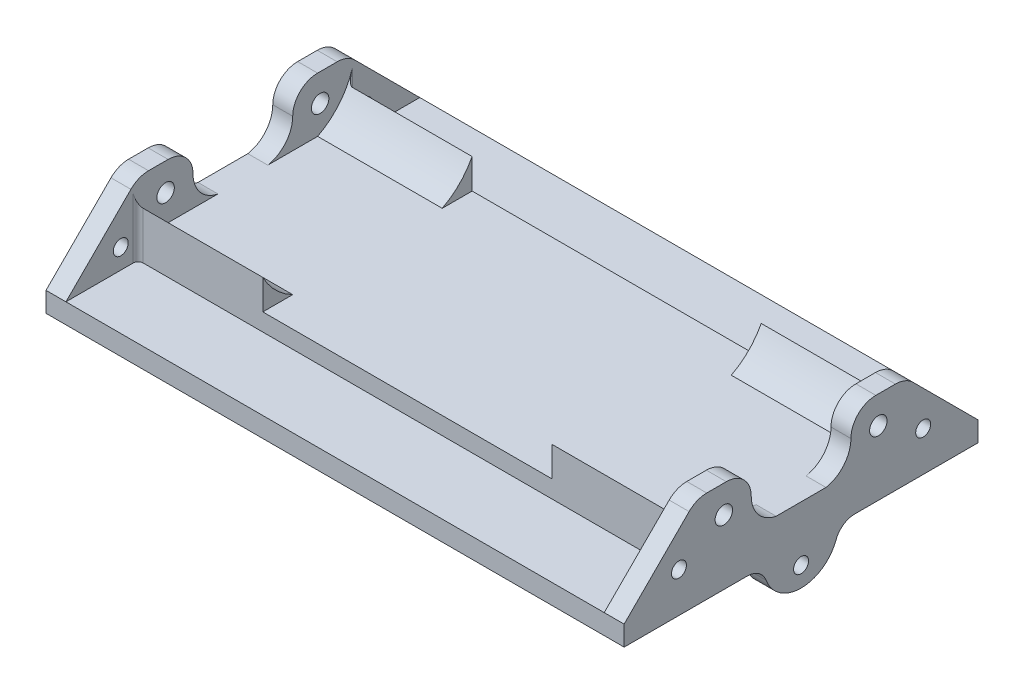
SolidWorks part; units mm, degrees
ref_plane "Front Plane" through (0, 0, 0) normal (0, 0, 1) x (1, 0, 0)
ref_plane "Top Plane" through (0, 0, 0) normal (0, 1, 0) x (1, 0, 0)
ref_plane "Right Plane" through (0, 0, 0) normal (1, 0, 0) x (0, 0, -1)
sketch "Sketch1" plane through (0, 0, 0) normal (0, 1, 0) x (1, 0, 0)
  line L1 (-58, -21) -> (58, -21)
  line L2 (-58, -21) -> (-58, 21)
  line L3 (-58, 21) -> (58, 21)
  line L4 (58, -21) -> (58, 21)
  line L5 (-58, -21) -> (58, 21) construction
  line L6 (-58, 21) -> (58, -21) construction
  point P0 (0, 0)
  dimension "D1" = 42
  dimension "D2" = 116
extrude "Boss-Extrude1" add sketch "Sketch1" along normal blind 3.5 from offset 3.5
sketch "Sketch2" plane through (0, 0, 0) normal (1, 0, 0) x (0, 0, -1)
  line L0 (-21, 7) -> (21, 7) construction
  line L1 (-21, 7) -> (21, 7)
  line L2 (0, 0) -> (0, 30.7392) construction
  line L3 (-21, 7) -> (-21, 54.5)
  line L4 (21, 7) -> (21, 54.5)
  line L5 (21, 48.95) -> (-21, 48.95)
  line L6 (21, 30.75) -> (-29.0104, 30.75) construction
  line L7 (21, 7) -> (10, 7)
  line L8 (21, 7) -> (21, 18)
  line L9 (21, 18) -> (15, 18)
  line L11 (10, 7) -> (0, 7)
  line L12 (-21, 18) -> (-15, 18)
  arc A0 (15, 18) -> (10, 13) centre (15, 13) ccw
  arc A1 (10, 13) -> (5, 7) centre (3.9, 13) cw
  arc A2 (-10, 13) -> (-5, 7) centre (-3.9, 13) ccw
  arc A3 (-15, 18) -> (-10, 13) centre (-15, 13) cw
  point P16 (10, 18)
  line B0 (-25, 54.5) -> (-25, 39.5)
  line B1 (25, 54.5) -> (-25, 54.5)
  line B2 (25, 54.5) -> (25, 39.5)
  line B3 (25, 7) -> (25, 39.5)
  line B4 (25, 7) -> (-25, 7)
  line B5 (-25, 7) -> (-25, 39.5)
  circle B6 centre (-15.5, 43.475) radius 1.75
  circle B7 centre (15.5, 43.475) radius 1.75
  circle B8 centre (15.5, 12.475) radius 1.75
  circle B9 centre (0, 27.975) radius 11.075
  circle B10 centre (-15.5, 12.475) radius 1.75
  dimension "D3" = 5
  dimension "D1" = 41.95
  dimension "D2" = 11
sketch_block_instance "Block1-2"
sketch_block "Block1"
extrude "Boss-Extrude2" add sketch "Sketch2" along normal up to surface and the other way up to surface contours A0 A1 L11 L1 L4 L9 B8 | A3 L12 L3 L1 A2 B10 region at (0, 12.5, 20.8058) region at (0, 8.9706, -8.7353) up to face at (58, 5.25, 0) other way up to face at (-58, 5.25, 0)
extrude "Cut-Extrude1" cut sketch "Sketch2<3>" against normal mid plane 108 contours A0 A1 L11 L1 L4 L9 B8 | A3 L12 L3 L1 A2 B10 region at (0, 12.5, 20.8058) region at (0, 8.9706, -8.7353)
sketch "Sketch2<3>" plane through (0, 0, 0) normal (1, 0, 0) x (0, 0, -1) same geometry as "Sketch2"
sketch "Sketch3" plane through (-54, 0, 0) normal (1, 0, 0) x (0, 0, -1)
  line L0 (-21, 7) -> (-15, 7)
  line L1 (-21, 7) -> (-21, 13)
  line L2 (-21, 18) -> (-21, 3.5) construction
  line L3 (0, 0) -> (0, 17.1319) construction
  line L4 (21, 7) -> (21, 13)
  line L5 (21, 7) -> (15, 7)
  arc A0 (-15, 7) -> (-21, 13) centre (-8.566, 19.434) cw
  arc A1 (15, 7) -> (21, 13) centre (8.566, 19.434) ccw
  dimension "D3" = 14
  dimension "D1" = 6
  dimension "D2" = 6
extrude "Boss-Extrude3" add sketch "Sketch3" along normal blind 25
mirror "Mirror4" about plane through (0, 0, 0) normal (1, 0, 0) of "Boss-Extrude3"
sketch "Sketch4" plane through (-58, 0, 0) normal (-1, 0, 0) x (0, 0, 1)
  line L0 (21, 18) -> (35.5, 3.5)
  line L1 (35.5, 3.5) -> (21, 3.5)
  line L2 (0, 3.5) -> (0, 12.4204) construction
  line L3 (-21, 3.5) -> (21, 3.5) construction
  line L4 (21, 18) -> (21, 3.5)
  line L5 (-21, 18) -> (-21, 3.5)
  line L6 (-35.5, 3.5) -> (-21, 3.5)
  line L7 (-21, 18) -> (-35.5, 3.5)
  circle A0 centre (24.5, 7.5) radius 1.5
  circle A1 centre (-24.5, 7.5) radius 1.5
  dimension "D2" = 3
  dimension "D1" = 14.5
  dimension "D3" = 4
  dimension "D4" = 3.5
extrude "Boss-Extrude5" add sketch "Sketch4" against normal up to surface (4 mm away) up to face at (-54, 12.475, -17.25)
sketch "Sketch5" plane through (58, 0, 0) normal (1, 0, 0) x (0, 0, -1)
  line L0 (-35.5, 3.5) -> (-21, 18) construction
  line L1 (-21, 3.5) -> (-35.5, 3.5) construction
  line L2 (-21, 18) -> (-21, 3.5) construction
  line L3 (21, 18) -> (21, 3.5) construction
  line L4 (21, 18) -> (35.5, 3.5) construction
  line L5 (35.5, 3.5) -> (21, 3.5) construction
  line L6 (-35.5, 3.5) -> (-21, 18)
  line L7 (-21, 3.5) -> (-35.5, 3.5)
  line L8 (-21, 18) -> (-21, 3.5)
  line L9 (21, 18) -> (21, 3.5)
  line L10 (21, 18) -> (35.5, 3.5)
  line L11 (35.5, 3.5) -> (21, 3.5)
  circle A0 centre (-24.5, 7.5) radius 1.5 construction
  circle A1 centre (24.5, 7.5) radius 1.5 construction
  circle A2 centre (-24.5, 7.5) radius 1.5
  circle A3 centre (24.5, 7.5) radius 1.5
extrude "Boss-Extrude6" add sketch "Sketch5" against normal up to surface (4 mm away) up to face at (54, 12.475, -17.25)
fillet "Fillet1" radius 5 4 edges at (56, 18, 21) (56, 18, -21) (-56, 18, 21) (-56, 18, -21)
fillet "Fillet2" radius 1 4 edges at (54, 8.25, -21) (-54, 8.25, -21) (54, 8.25, 21) (-54, 8.25, 21)
sketch "Sketch6" plane through (0, 3.5, 0) normal (0, -1, 0) x (1, 0, 0)
  line L1 (-58, 35.5) -> (58, 35.5)
  line L2 (-58, 35.5) -> (-58, -35.5)
  line L3 (-58, -35.5) -> (58, -35.5)
  line L4 (58, 35.5) -> (58, -35.5)
extrude "Boss-Extrude7" add sketch "Sketch6" along normal blind 4
sketch "Sketch7" plane through (-58, 0, 0) normal (-1, 0, 0) x (0, 0, 1)
  line L11 (35.5, -0.5) -> (-35.5, -0.5) construction
  line L12 (7.5, -0.5) -> (-7.5, -0.5)
  arc A1 (7.5, -0.5) -> (-7.5, -0.5) centre (0, -0.5) cw
  circle A2 centre (0, -4) radius 1.5
  dimension "D2" = 3
  dimension "D1" = 7.5
  dimension "D3" = 3.5
extrude "Boss-Extrude8" add sketch "Sketch7" against normal blind 4
pattern_linear "LPattern1" count 2 spacing 112 along (1, 0, 0) of "Boss-Extrude8"
fillet "Fillet3" radius 4 4 edges at (-56, -0.5, 7.5) (-56, -0.5, -7.5) (56, -0.5, -7.5) (56, -0.5, 7.5)
sketch "Sketch8" plane through (58, 0, 0) normal (1, 0, 0) x (0, 0, -1)
  line L0 (-15, 18) -> (-18.9289, 18) construction
  line L1 (15, 18) -> (18.9289, 18) construction
  line L2 (-5, 7) -> (5, 7) construction
  line L3 (35.5, 3.5) -> (22.4645, 16.5355) construction
  line L4 (35.5, -0.5) -> (35.5, 3.5) construction
  line L5 (-22.4645, 16.5355) -> (-35.5, 3.5) construction
  line L6 (-35.5, -0.5) -> (-35.5, 3.5) construction
  line L7 (-10.7819, -0.5) -> (-35.5, -0.5) construction
  line L8 (35.5, -0.5) -> (10.7819, -0.5) construction
  line L9 (-15, 18) -> (-18.9289, 18)
  line L10 (15, 18) -> (18.9289, 18)
  line L11 (-5, 7) -> (5, 7)
  line L12 (35.5, 3.5) -> (22.4645, 16.5355)
  line L13 (35.5, -0.5) -> (35.5, 3.5)
  line L14 (-22.4645, 16.5355) -> (-35.5, 3.5)
  line L15 (-35.5, -0.5) -> (-35.5, 3.5)
  line L16 (-10.7819, -0.5) -> (-35.5, -0.5)
  line L17 (35.5, -0.5) -> (10.7819, -0.5)
  circle A0 centre (15.5, 12.475) radius 1.75 construction
  circle A1 centre (-15.5, 12.475) radius 1.75 construction
  arc A2 (-10, 13) -> (-5, 7) centre (-3.9, 13) ccw construction
  arc A3 (-10, 13) -> (-15, 18) centre (-15, 13) ccw construction
  arc A4 (-18.9289, 18) -> (-22.4645, 16.5355) centre (-18.9289, 13) ccw construction
  arc A5 (22.4645, 16.5355) -> (18.9289, 18) centre (18.9289, 13) ccw construction
  arc A6 (15, 18) -> (10, 13) centre (15, 13) ccw construction
  arc A7 (5, 7) -> (10, 13) centre (3.9, 13) ccw construction
  circle A8 centre (0, -4) radius 1.5 construction
  circle A9 centre (24.5, 7.5) radius 1.5 construction
  circle A10 centre (-24.5, 7.5) radius 1.5 construction
  arc A11 (-7.0317, -3.1087) -> (-10.7819, -0.5) centre (-10.7819, -4.5) ccw construction
  arc A12 (10.7819, -0.5) -> (7.0317, -3.1087) centre (10.7819, -4.5) ccw construction
  arc A13 (-7.0317, -3.1087) -> (7.0317, -3.1087) centre (0, -0.5) ccw construction
  circle A14 centre (15.5, 12.475) radius 1.75
  circle A15 centre (-15.5, 12.475) radius 1.75
  arc A16 (-10, 13) -> (-5, 7) centre (-3.9, 13) ccw
  arc A17 (-10, 13) -> (-15, 18) centre (-15, 13) ccw
  arc A18 (-18.9289, 18) -> (-22.4645, 16.5355) centre (-18.9289, 13) ccw
  arc A19 (22.4645, 16.5355) -> (18.9289, 18) centre (18.9289, 13) ccw
  arc A20 (15, 18) -> (10, 13) centre (15, 13) ccw
  arc A21 (5, 7) -> (10, 13) centre (3.9, 13) ccw
  circle A22 centre (0, -4) radius 1.5
  circle A23 centre (24.5, 7.5) radius 1.5
  circle A24 centre (-24.5, 7.5) radius 1.5
  arc A25 (-7.0317, -3.1087) -> (-10.7819, -0.5) centre (-10.7819, -4.5) ccw
  arc A26 (10.7819, -0.5) -> (7.0317, -3.1087) centre (10.7819, -4.5) ccw
  arc A27 (-7.0317, -3.1087) -> (7.0317, -3.1087) centre (0, -0.5) ccw
